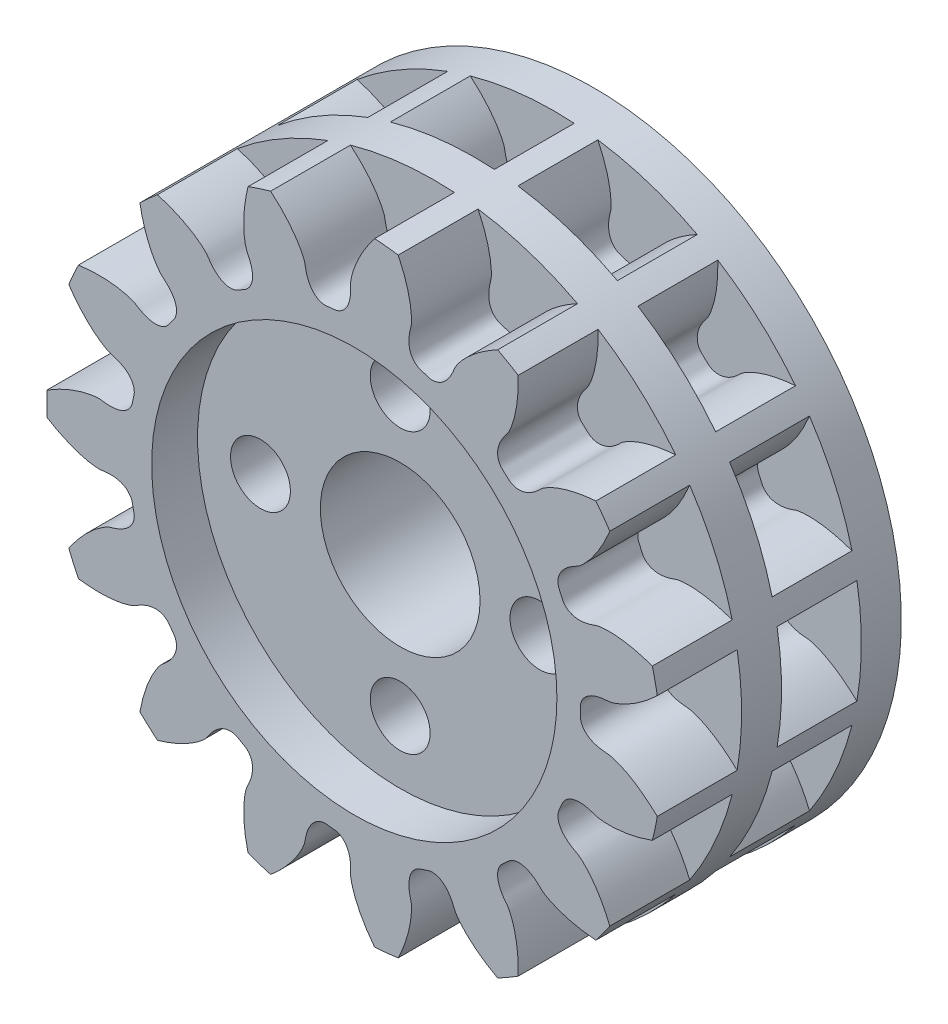
SolidWorks part; units mm, degrees
material "Д16 ГОСТ 4784-97"
ref_plane "FRONT" through (0, 0, 0) normal (0, 0, 1) x (1, 0, 0)
ref_plane "TOP" through (0, 0, 0) normal (0, 1, 0) x (1, 0, 0)
ref_plane "RIGHT" through (0, 0, 0) normal (1, 0, 0) x (0, 0, -1)
ref_axis "Ось1" through (0, 0, 50) along (0, 0, -1)
sketch "SketchRevolveSpurPinion" plane through (0, 0, 0) normal (1, 0, 0) x (0, 0, -1)
  line L0 (0, 0) -> (1, 0) construction
  line L1 (-5, 0) -> (-5, 15.402)
  line L2 (-5, 15.402) -> (5, 15.402)
  line L3 (5, 15.402) -> (5, 0)
  line L4 (5, 0) -> (-5, 0)
  dimension "D1" = 10
revolve "SpurPinion" add sketch "SketchRevolveSpurPinion" angle 360 about L0
sketch "SketchToothSpurPinion" plane through (0, 0, 5) normal (0, 0, 1) x (1, 0, 0)
  arc A0 (15.2565, 2.6946) -> (15.2565, -2.6946) centre (0, 0) cw
  spline S0 degree 3 poles (15.2565, -2.6946) (15.1204, -2.5609) (14.9153, -2.3721) (14.6367, -2.1416) (14.4399, -1.9898) (14.2503, -1.8536) (14.0686, -1.7324) (13.8956, -1.6254) (13.7322, -1.5319) (13.579, -1.451) (13.4367, -1.382) (13.3058, -1.3241) (13.187, -1.2763) (13.0808, -1.2377) (12.9877, -1.2074) (12.9081, -1.1847) (12.7384, -1.1404) (12.5726, -1.1422) (12.4172, -1.1217) (12.3702, -1.1147) (12.324, -1.1069) (12.2785, -1.0982) (12.2338, -1.0887) (12.1899, -1.0783) (12.1467, -1.067) (12.1042, -1.0548) (12.0624, -1.0418) (12.0213, -1.0278) (11.9809, -1.0128) (11.9412, -0.9968) (11.9021, -0.9798) (11.8637, -0.9616) (11.8259, -0.9423) (11.7887, -0.9218) (11.7522, -0.8999) (11.7163, -0.8766) (11.681, -0.8517) (11.6465, -0.8253) (11.6127, -0.797) (11.5797, -0.7668) (11.5476, -0.7346) (11.5166, -0.7002) (11.4868, -0.6634) (11.4585, -0.6241) (11.4319, -0.5823) (11.4073, -0.5379) (11.3852, -0.4909) (11.3658, -0.4414) (11.3496, -0.3895) (11.337, -0.3357) (11.3282, -0.2803) (11.3242, -0.2287) (11.3226, -0.1352) (11.3269, 0) (11.3226, 0.1352) (11.3242, 0.2287) (11.3282, 0.2803) (11.337, 0.3357) (11.3496, 0.3895) (11.3658, 0.4414) (11.3852, 0.4909) (11.4073, 0.5379) (11.4319, 0.5823) (11.4585, 0.6241) (11.4868, 0.6634) (11.5166, 0.7002) (11.5476, 0.7346) (11.5797, 0.7668) (11.6127, 0.797) (11.6465, 0.8253) (11.681, 0.8517) (11.7163, 0.8766) (11.7522, 0.8999) (11.7887, 0.9218) (11.8259, 0.9423) (11.8637, 0.9616) (11.9021, 0.9798) (11.9412, 0.9968) (11.9809, 1.0128) (12.0213, 1.0278) (12.0624, 1.0418) (12.1042, 1.0548) (12.1467, 1.067) (12.1899, 1.0783) (12.2338, 1.0887) (12.2785, 1.0982) (12.324, 1.1069) (12.3702, 1.1147) (12.4172, 1.1217) (12.5726, 1.1422) (12.7384, 1.1404) (12.9081, 1.1847) (12.9877, 1.2074) (13.0808, 1.2377) (13.187, 1.2763) (13.3058, 1.3241) (13.4367, 1.382) (13.579, 1.451) (13.7322, 1.5319) (13.8956, 1.6254) (14.0686, 1.7324) (14.2503, 1.8536) (14.4399, 1.9898) (14.6367, 2.1416) (14.9153, 2.3721) (15.1204, 2.5609) (15.2565, 2.6946) knots 0 0 0 0 0.056361 0.082316 0.106788 0.129777 0.151283 0.171306 0.189846 0.206902 0.222476 0.236566 0.249173 0.260297 0.269937 0.278095 0.284769 0.321669 0.326412 0.33109 0.335705 0.340261 0.34476 0.349206 0.353603 0.357953 0.362262 0.366534 0.370775 0.37499 0.379185 0.383368 0.387544 0.391724 0.395914 0.400124 0.404365 0.408647 0.41298 0.417377 0.421849 0.426407 0.431063 0.435825 0.440701 0.445696 0.450813 0.456049 0.461396 0.466842 0.472369 0.477956 0.4821 0.5 0.5179 0.522044 0.527631 0.533158 0.538604 0.543951 0.549187 0.554304 0.559299 0.564175 0.568937 0.573593 0.578151 0.582623 0.58702 0.591353 0.595635 0.599876 0.604086 0.608276 0.612456 0.616632 0.620815 0.62501 0.629225 0.633466 0.637738 0.642047 0.646397 0.650794 0.65524 0.659739 0.664295 0.66891 0.673588 0.678331 0.715231 0.721905 0.730063 0.739703 0.750827 0.763434 0.777524 0.793098 0.810154 0.828694 0.848717 0.870223 0.893212 0.917684 0.943639 1 1 1 1
extrude "ToothExtrudeCutSpurPinion" cut sketch "SketchToothSpurPinion" against normal blind 4 from offset 0
pattern_circular "PatternSpurPinion" count 15 every 24 about axis through (0, 0, 50) along (0, 0, -1) of "ToothExtrudeCutSpurPinion"
sketch "AuxiliarySketchSpurPinion" plane through (0, 0, 0) normal (0, 0, 1) x (1, 0, 0)
  circle A0 centre (0, 0) radius 13.59 construction
  circle A1 centre (0, 0) radius 12.7704 construction
  circle A2 centre (0, 0) radius 12.8041 construction
  circle A3 centre (0, 0) radius 15.402 construction
  circle A4 centre (0, 0) radius 11.325 construction
  dimension "PitchDiameter" = 27.18
  dimension "BaseDiameter" = 25.5408
  dimension "FormDiameter" = 25.6083
  dimension "MajorDiameter" = 30.804
  dimension "MinorDiameter" = 22.65
sketch "Эскиз5" plane through (0, 0, 5) normal (0, 0, 1) x (1, 0, 0)
  circle A0 centre (0, 0) radius 10.15
  dimension "D1" = 20.3
extrude "Вырез-Вытянуть2" cut sketch "Эскиз5" against normal blind 2.3
sketch "Эскиз8" plane through (0, 0, -5) normal (0, 0, 1) x (1, 0, 0)
  arc A0 (15.2565, 2.6946) -> (15.2565, -2.6946) centre (0, 0) cw
  spline S0 degree 3 poles (15.2565, -2.6946) (15.1204, -2.5609) (14.9153, -2.3721) (14.6367, -2.1416) (14.4399, -1.9898) (14.2503, -1.8536) (14.0686, -1.7324) (13.8956, -1.6254) (13.7322, -1.5319) (13.579, -1.451) (13.4367, -1.382) (13.3058, -1.3241) (13.187, -1.2763) (13.0808, -1.2377) (12.9877, -1.2074) (12.9081, -1.1847) (12.7384, -1.1404) (12.5726, -1.1422) (12.4172, -1.1217) (12.3702, -1.1147) (12.324, -1.1069) (12.2785, -1.0982) (12.2338, -1.0887) (12.1899, -1.0783) (12.1467, -1.067) (12.1042, -1.0548) (12.0624, -1.0418) (12.0213, -1.0278) (11.9809, -1.0128) (11.9412, -0.9968) (11.9021, -0.9798) (11.8637, -0.9616) (11.8259, -0.9423) (11.7887, -0.9218) (11.7522, -0.8999) (11.7163, -0.8766) (11.681, -0.8517) (11.6465, -0.8253) (11.6127, -0.797) (11.5797, -0.7668) (11.5476, -0.7346) (11.5166, -0.7002) (11.4868, -0.6634) (11.4585, -0.6241) (11.4319, -0.5823) (11.4073, -0.5379) (11.3852, -0.4909) (11.3658, -0.4414) (11.3496, -0.3895) (11.337, -0.3357) (11.3282, -0.2803) (11.3242, -0.2287) (11.3226, -0.1352) (11.3269, 0) (11.3226, 0.1352) (11.3242, 0.2287) (11.3282, 0.2803) (11.337, 0.3357) (11.3496, 0.3895) (11.3658, 0.4414) (11.3852, 0.4909) (11.4073, 0.5379) (11.4319, 0.5823) (11.4585, 0.6241) (11.4868, 0.6634) (11.5166, 0.7002) (11.5476, 0.7346) (11.5797, 0.7668) (11.6127, 0.797) (11.6465, 0.8253) (11.681, 0.8517) (11.7163, 0.8766) (11.7522, 0.8999) (11.7887, 0.9218) (11.8259, 0.9423) (11.8637, 0.9616) (11.9021, 0.9798) (11.9412, 0.9968) (11.9809, 1.0128) (12.0213, 1.0278) (12.0624, 1.0418) (12.1042, 1.0548) (12.1467, 1.067) (12.1899, 1.0783) (12.2338, 1.0887) (12.2785, 1.0982) (12.324, 1.1069) (12.3702, 1.1147) (12.4172, 1.1217) (12.5726, 1.1422) (12.7384, 1.1404) (12.9081, 1.1847) (12.9877, 1.2074) (13.0808, 1.2377) (13.187, 1.2763) (13.3058, 1.3241) (13.4367, 1.382) (13.579, 1.451) (13.7322, 1.5319) (13.8956, 1.6254) (14.0686, 1.7324) (14.2503, 1.8536) (14.4399, 1.9898) (14.6367, 2.1416) (14.9153, 2.3721) (15.1204, 2.5609) (15.2565, 2.6946) knots 0 0 0 0 0.056361 0.082316 0.106788 0.129777 0.151283 0.171306 0.189846 0.206902 0.222476 0.236566 0.249173 0.260297 0.269937 0.278095 0.284769 0.321669 0.326412 0.33109 0.335705 0.340261 0.34476 0.349206 0.353603 0.357953 0.362262 0.366534 0.370775 0.37499 0.379185 0.383368 0.387544 0.391724 0.395914 0.400124 0.404365 0.408647 0.41298 0.417377 0.421849 0.426407 0.431063 0.435825 0.440701 0.445696 0.450813 0.456049 0.461396 0.466842 0.472369 0.477956 0.4821 0.5 0.5179 0.522044 0.527631 0.533158 0.538604 0.543951 0.549187 0.554304 0.559299 0.564175 0.568937 0.573593 0.578151 0.582623 0.58702 0.591353 0.595635 0.599876 0.604086 0.608276 0.612456 0.616632 0.620815 0.62501 0.629225 0.633466 0.637738 0.642047 0.646397 0.650794 0.65524 0.659739 0.664295 0.66891 0.673588 0.678331 0.715231 0.721905 0.730063 0.739703 0.750827 0.763434 0.777524 0.793098 0.810154 0.828694 0.848717 0.870223 0.893212 0.917684 0.943639 1 1 1 1
extrude "Вырез-Вытянуть4" cut sketch "Эскиз8" along normal blind 4
pattern_circular "Круговой массив1" count 15 over 360 about axis through (0, 0, -5) along (0, 0, 1) of "Вырез-Вытянуть4"
sketch "Эскиз9" plane through (0, 0, -5) normal (0, 0, -1) x (-1, 0, 0)
  circle A0 centre (0, 0) radius 15.402
extrude "Бобышка-Вытянуть1" add sketch "Эскиз9" along normal blind 2
sketch "Эскиз6" plane through (0, 0, 2.7) normal (0, 0, 1) x (1, 0, 0)
  circle A0 centre (0, 0) radius 7 construction
  circle A1 centre (0, 0) radius 8.5 construction
  circle A3 centre (0, 7) radius 1.5
  circle A4 centre (7, 0) radius 1.5
  circle A5 centre (0, -7) radius 1.5
  circle A6 centre (-7, 0) radius 1.5
  circle A7 centre (0, 0) radius 4
  dimension "D1" = 14
  dimension "D2" = 17
  dimension "D3" = 8
extrude "Вырез-Вытянуть3" cut sketch "Эскиз6" against normal through all and the other way through all
